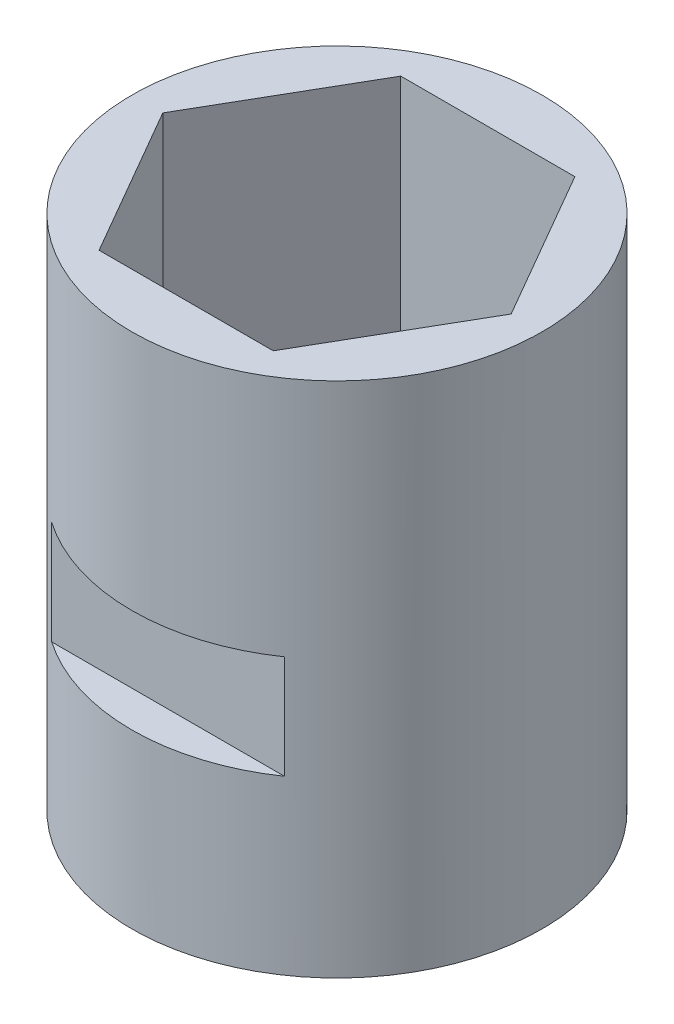
SolidWorks part; units mm, degrees
material "Polyester Resin"
ref_plane "Front Plane" through (0, 0, 0) normal (0, 0, 1) x (1, 0, 0)
ref_plane "Top Plane" through (0, 0, 0) normal (0, 1, 0) x (1, 0, 0)
ref_plane "Right Plane" through (0, 0, 0) normal (1, 0, 0) x (0, 0, -1)
sketch "Sketch1" plane through (0, 0, 0) normal (0, 1, 0) x (1, 0, 0)
  line L1 (-3.2079, 5.5563) -> (-6.4158, 0)
  line L2 (-6.4158, 0) -> (-3.2079, -5.5562)
  line L3 (-3.2079, -5.5562) -> (3.2079, -5.5562)
  line L4 (3.2079, -5.5562) -> (6.4158, 0)
  line L5 (6.4158, 0) -> (3.2079, 5.5563)
  line L6 (3.2079, 5.5563) -> (-3.2079, 5.5563)
  circle A0 centre (0, 0) radius 5.5562 construction
  circle A1 centre (0, 0) radius 7.5565
  dimension "D2" = 15.113
  dimension "D1" = 11.1125
extrude "Boss-Extrude1" add sketch "Sketch1" along normal blind 15.875
sketch "Sketch2" plane through (0, 0, 0) normal (0, -1, 0) x (1, 0, 0)
  circle A0 centre (0, 0) radius 7.5565
  circle A1 centre (0, 0) radius 3.3782
  dimension "D1" = 6.7564
extrude "Boss-Extrude2" add sketch "Sketch2" along normal blind 3.175
sketch "Sketch3" plane through (0, 0, 0) normal (1, 0, 0) x (0, 0, -1)
  line L0 (-6.223, 6.985) -> (-6.223, 3.175)
  line L1 (6.223, 6.985) -> (6.223, 3.175)
  line L2 (-7.5565, -3.175) -> (7.5565, -3.175) construction
  line L3 (-6.223, 6.985) -> (-8.202, 6.985)
  line L4 (-8.202, 6.985) -> (-8.202, 3.175)
  line L5 (-8.202, 3.175) -> (-6.223, 3.175)
  line L6 (6.223, 6.985) -> (8.4791, 6.985)
  line L7 (8.4791, 6.985) -> (8.4791, 3.175)
  line L8 (8.4791, 3.175) -> (6.223, 3.175)
  dimension "D1" = 12.446
  dimension "D2" = 6.223
  dimension "D3" = 3.81
  dimension "D4" = 3.81
  dimension "D5" = 6.35
  dimension "D6" = 6.35
extrude "Cut-Extrude1" cut sketch "Sketch3" against normal through all and the other way through all
equation "\"AB_Central_Bushing_Length\" = .75in"
equation "\"Solid_Length\"= .125in"
equation "\"Hex_Length\" = \"AB_Central_Bushing_Length\" - \"Solid_Length\""
equation "\"D1@Boss-Extrude1\"=\"Hex_Length\""
equation "\"D1@Boss-Extrude2\"=\"Solid_Length\""
equation "\"Cutout_Angle\" = 80"
